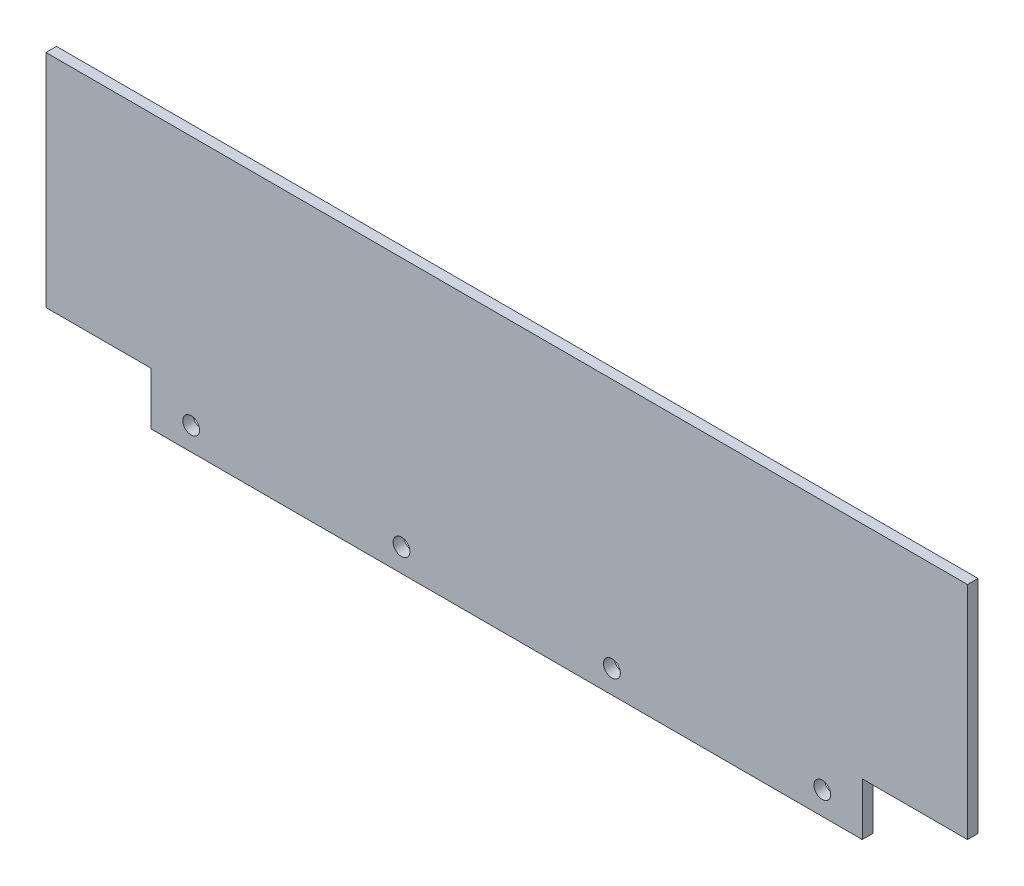
SolidWorks part; units mm, degrees
ref_plane "Alzado" through (0, 0, 0) normal (0, 0, 1) x (1, 0, 0)
ref_plane "Planta" through (0, 0, 0) normal (0, 1, 0) x (1, 0, 0)
ref_plane "Vista lateral" through (0, 0, 0) normal (1, 0, 0) x (0, 0, -1)
sketch "Croquis1" plane through (0, 0, 0) normal (0, 0, 1) x (1, 0, 0)
  line L0 (0, 0) -> (-338, 0)
  line L1 (-338, 0) -> (-338, 25)
  line L2 (-338, 25) -> (-388, 25)
  line L3 (-388, 25) -> (-388, 130)
  line L4 (-388, 130) -> (50, 130)
  line L5 (50, 130) -> (50, 25)
  line L6 (50, 25) -> (0, 25)
  line L7 (0, 25) -> (0, 0)
  line L8 (415.9078, 25) -> (-728.0032, 25) construction
  line L9 (44.691, 11) -> (-362.5608, 11) construction
  line L11 (-169, 130) -> (-169, -50.4144) construction
  circle A0 centre (-319, 11) radius 4
  circle A1 centre (-219, 11) radius 4
  circle A2 centre (-119, 11) radius 4
  circle A3 centre (-19, 11) radius 4
  dimension "D12" = 8
  dimension "D1" = 338
  dimension "D2" = 25
  dimension "D3" = 50
  dimension "D4" = 50
  dimension "D5" = 105
  dimension "D6" = 11
  dimension "D9" = 100
  dimension "D10" = 100
  dimension "D11" = 100
  dimension "D18" = 50
extrude "Saliente-Extruir1" add sketch "Croquis1" along normal blind 5
